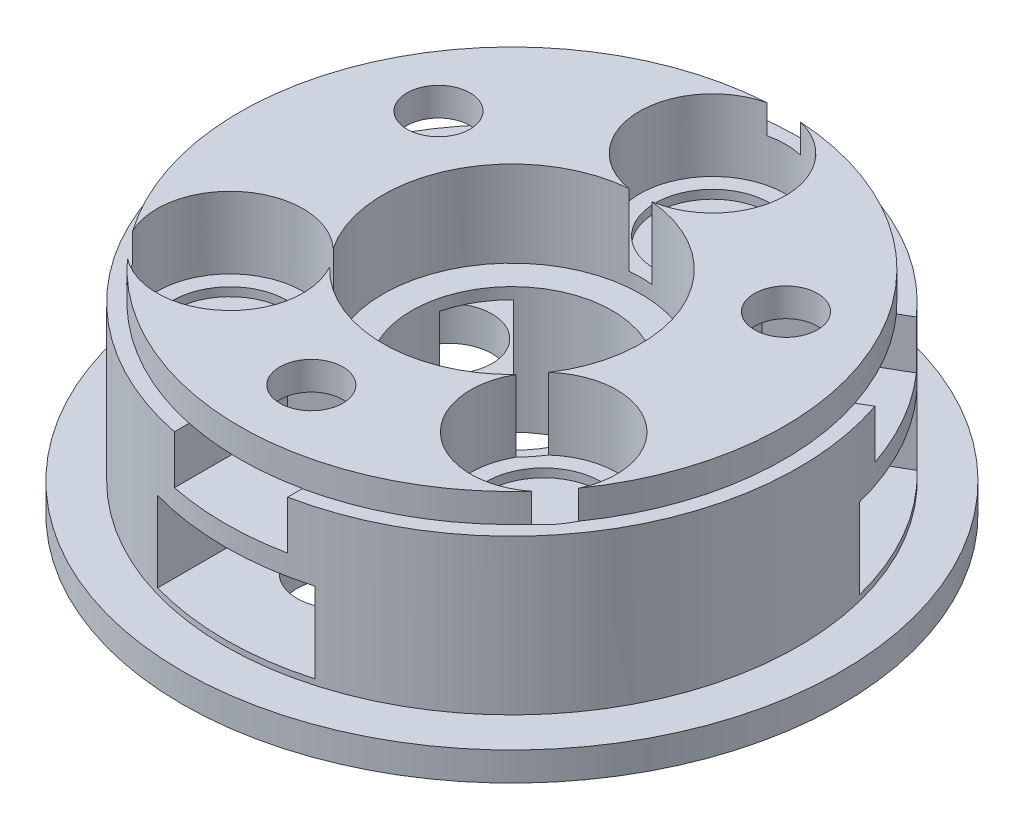
SolidWorks part; units mm, degrees
ref_plane "Front Plane" through (0, 0, 0) normal (0, 0, 1) x (1, 0, 0)
ref_plane "Top Plane" through (0, 0, 0) normal (0, 1, 0) x (1, 0, 0)
ref_plane "Right Plane" through (0, 0, 0) normal (1, 0, 0) x (0, 0, -1)
sketch "Sketch2" plane through (0, 0, 0) normal (0, 1, 0) x (1, 0, 0)
  circle A0 centre (0, 0) radius 11.5
  dimension "D1" = 23
extrude "Boss-Extrude1" add sketch "Sketch2" along normal blind 1
sketch "Sketch3" plane through (0, 1, 0) normal (0, 1, 0) x (1, 0, 0)
  circle A0 centre (0, 0) radius 10
  dimension "D1" = 20
extrude "Boss-Extrude2" add sketch "Sketch3" along normal blind 4
ref_plane "Plane1" through (0, 4.9, 0) normal (0, -1, 0) x (-1, 0, 0)
sketch "Sketch4" plane through (0, 4.9, 0) normal (0, -1, 0) x (-1, 0, 0)
  circle A0 centre (0, 0) radius 7 construction
  circle A1 centre (0, 7) radius 2.55
  dimension "D1" = 14
  dimension "D2" = 5.1
extrude "Cut-Extrude1" cut sketch "Sketch4" against normal through all
sketch "Sketch5" plane through (0, 4.9, 0) normal (0, 1, 0) x (1, 0, 0)
  circle A0 centre (0, 7) radius 2
  dimension "D1" = 4
extrude "Cut-Extrude2" cut sketch "Sketch5" against normal blind 0.3
ref_axis "Axis1" through (0, 5, 0) along (0, -1, 0)
pattern_circular "CirPattern1" count 14 over 360 about axis through (0, 5, 0) along (0, -1, 0) skipping 1, 2, 3, 4, 6, 7, 8, 10, 11, 12, 13 of "Cut-Extrude1", "Cut-Extrude2"
sketch "Sketch7" plane through (0, 4.9, 0) normal (0, 1, 0) x (1, 0, 0)
  circle A0 centre (5.4728, -4.3644) radius 2.55 construction
  circle A1 centre (0, 0) radius 10
  circle A3 centre (-5.4728, -4.3644) radius 2.55 construction
  circle A4 centre (0, 7) radius 2.55 construction
  circle A5 centre (5.4728, -4.3644) radius 2.55
  circle A6 centre (-5.4728, -4.3644) radius 2.55
  circle A7 centre (0, 7) radius 2.55
  circle A9 centre (0, 0) radius 10
  dimension "D1" = 0
extrude "Boss-Extrude4" add sketch "Sketch7" along normal blind 1.5
sketch "Sketch6" plane through (0, 6.4, 0) normal (0, 1, 0) x (1, 0, 0)
  circle A0 centre (0, 0) radius 4.5 construction
  arc A1 (-0.5851, 9.482) -> (-0.4025, 4.482) centre (0, 7) ccw
  circle A2 centre (0, 0) radius 9.5 construction
  arc A3 (-3.7551, -2.4798) -> (-7.7781, -5.4545) centre (-5.4728, -4.3644) ccw
  arc A4 (3.2532, -3.1091) -> (7.0485, -6.3694) centre (5.4728, -4.3644) ccw
  arc A5 (0.4025, 4.482) -> (0.5851, 9.482) centre (0, 7) ccw
  arc A6 (-7.0485, -6.3694) -> (-3.2532, -3.1091) centre (-5.4728, -4.3644) ccw
  arc A7 (7.7781, -5.4545) -> (3.7551, -2.4798) centre (5.4728, -4.3644) ccw
  arc A8 (-3.7551, -2.4798) -> (-0.4025, 4.482) centre (0, 0) cw
  arc A9 (-7.7781, -5.4545) -> (-0.5851, 9.482) centre (0, 0) cw
  arc A12 (-3.2532, -3.1091) -> (3.2532, -3.1091) centre (0, 0) ccw
  arc A13 (-7.0485, -6.3694) -> (7.0485, -6.3694) centre (0, 0) ccw
  arc A14 (0.4025, 4.482) -> (3.7551, -2.4798) centre (0, 0) cw
  arc A15 (0.5851, 9.482) -> (7.7781, -5.4545) centre (0, 0) cw
  dimension "D1" = 9
  dimension "D2" = 5.1
  dimension "D3" = 19
extrude "Boss-Extrude3" add sketch "Sketch6" along normal up to surface (0.998 mm away)
sketch "Sketch8" plane through (0, 7.398, 0) normal (0, 1, 0) x (1, 0, 0)
  circle A0 centre (0, -7) radius 1.1 construction
  circle A1 centre (0, -7) radius 1.1
extrude "Cut-Extrude3" cut sketch "Sketch8" against normal offset from surface (2.69 mm away) 12.2
sketch "Sketch9" plane through (0, 4.708, 0) normal (0, 1, 0) x (1, 0, 0)
  line L0 (-1.975, -8.1403) -> (-1.975, -11.3291)
  line L1 (0, -9.2805) -> (1.975, -8.1403) construction
  line L2 (1.975, -8.1403) -> (1.975, -5.8597)
  line L3 (1.975, -5.8597) -> (0, -4.7195)
  line L4 (0, -4.7195) -> (-1.975, -5.8597)
  line L5 (-1.975, -5.8597) -> (-1.975, -8.1403)
  line L6 (-1.975, -8.1403) -> (0, -9.2805) construction
  line L7 (-1.975, -11.3291) -> (1.975, -11.3291)
  line L8 (1.975, -11.3291) -> (1.975, -8.1403)
  circle A0 centre (0, -7) radius 1.975 construction
  circle A1 centre (0, 0) radius 11.5 construction
  dimension "D1" = 3.95
extrude "Cut-Extrude4" cut sketch "Sketch9" along normal blind 1.7 contours L7 L8 L2 L3 L4 L5 L0
pattern_circular "CirPattern2" count 3 over 360 about axis through (0, 5, 0) along (0, -1, 0) of "Cut-Extrude4", "Cut-Extrude3"
sketch "Sketch10" plane through (0, 0, 0) normal (0, -1, 0) x (1, 0, 0)
  circle A0 centre (0, 0) radius 8 construction
  circle A1 centre (0, 8) radius 1.35
  dimension "D1" = 16
  dimension "D2" = 2.7
sketch "Sketch11" [suppressed] plane through (0, 0, 0) normal (0, -1, 0) x (1, 0, 0)
  circle A1 centre (0, 0) radius 11.5
  circle A2 centre (0, 0) radius 11.5
  dimension "D1" = 0
extrude "Boss-Extrude5" [suppressed] add sketch "Sketch11" along normal blind 3
sketch "Sketch12" [suppressed] plane through (0, -3, 0) normal (0, -1, 0) x (1, 0, 0)
  circle A0 centre (0, 8) radius 1.65
  dimension "D1" = 3.3
extrude "Cut-Extrude5" [suppressed] cut sketch "Sketch12" against normal up to surface (4 mm away) up to face at (0, 1, 10)
sketch "Sketch13" [suppressed] plane through (0, 1, 0) normal (0, 1, 0) x (1, 0, 0)
  line L0 (-2.75, -9.5877) -> (-2.75, -11.5)
  line L1 (0, -11.1754) -> (2.75, -9.5877) construction
  line L2 (2.75, -9.5877) -> (2.75, -6.4123)
  line L3 (2.75, -6.4123) -> (0, -4.8246)
  line L4 (0, -4.8246) -> (-2.75, -6.4123)
  line L5 (-2.75, -6.4123) -> (-2.75, -9.5877)
  line L6 (-2.75, -9.5877) -> (0, -11.1754) construction
  line L7 (-2.75, -11.5) -> (2.75, -11.5)
  line L8 (2.75, -11.5) -> (2.75, -9.5877)
  circle A0 centre (0, -8) radius 2.75 construction
  circle A1 centre (0, 0) radius 11.5 construction
  dimension "D1" = 5.5
extrude "Cut-Extrude6" [suppressed] cut sketch "Sketch13" against normal blind 2.8
pattern_circular "CirPattern3" [suppressed] count 4 over 360 about axis through (0, 5, 0) along (0, -1, 0) of bodies 114
sketch "Sketch14" plane through (0, 0, 0) normal (0, -1, 0) x (1, 0, 0)
  circle A0 centre (0, 0) radius 6 construction
  circle A1 centre (0, 6) radius 1.5
  dimension "D1" = 12
  dimension "D2" = 3
extrude "Cut-Extrude7" cut sketch "Sketch14" against normal blind 4
sketch "Sketch15" plane through (0, 4, 0) normal (0, -1, 0) x (1, 0, 0)
  line L1 (0, 2.8246) -> (2.75, 4.4123)
  line L2 (2.75, 4.4123) -> (2.75, 7.5877)
  line L3 (2.75, 7.5877) -> (0, 9.1754) construction
  line L4 (0, 9.1754) -> (-2.75, 7.5877) construction
  line L5 (-2.75, 7.5877) -> (-2.75, 4.4123)
  line L6 (-2.75, 4.4123) -> (0, 2.8246)
  line L9 (2.75, 11.5) -> (-2.75, 11.5)
  line L10 (-2.75, 7.5877) -> (-2.75, 11.5)
  line L11 (2.75, 7.5877) -> (2.75, 11.5)
  circle A0 centre (0, 6) radius 2.75 construction
  circle A2 centre (0, 0) radius 11.5 construction
  dimension "D1" = 5.5
extrude "Cut-Extrude8" cut sketch "Sketch15" along normal blind 2.8
pattern_circular "CirPattern4" count 3 over 360 about axis through (0, 5, 0) along (0, -1, 0) of "Cut-Extrude7", "Cut-Extrude8"
sketch "Sketch16" plane through (0, 6.4, 0) normal (0, 1, 0) x (1, 0, 0)
  circle A0 centre (0, 0) radius 4.5
  arc A1 (3.7551, -2.4798) -> (0.4025, 4.482) centre (0, 0) ccw construction
extrude "Cut-Extrude9" cut sketch "Sketch16" against normal blind 2
sketch "Sketch17" plane through (0, 4.4, 0) normal (0, 1, 0) x (1, 0, 0)
  circle A0 centre (0, 0) radius 3.5
  dimension "D1" = 7
extrude "Cut-Extrude10" cut sketch "Sketch17" against normal through all
